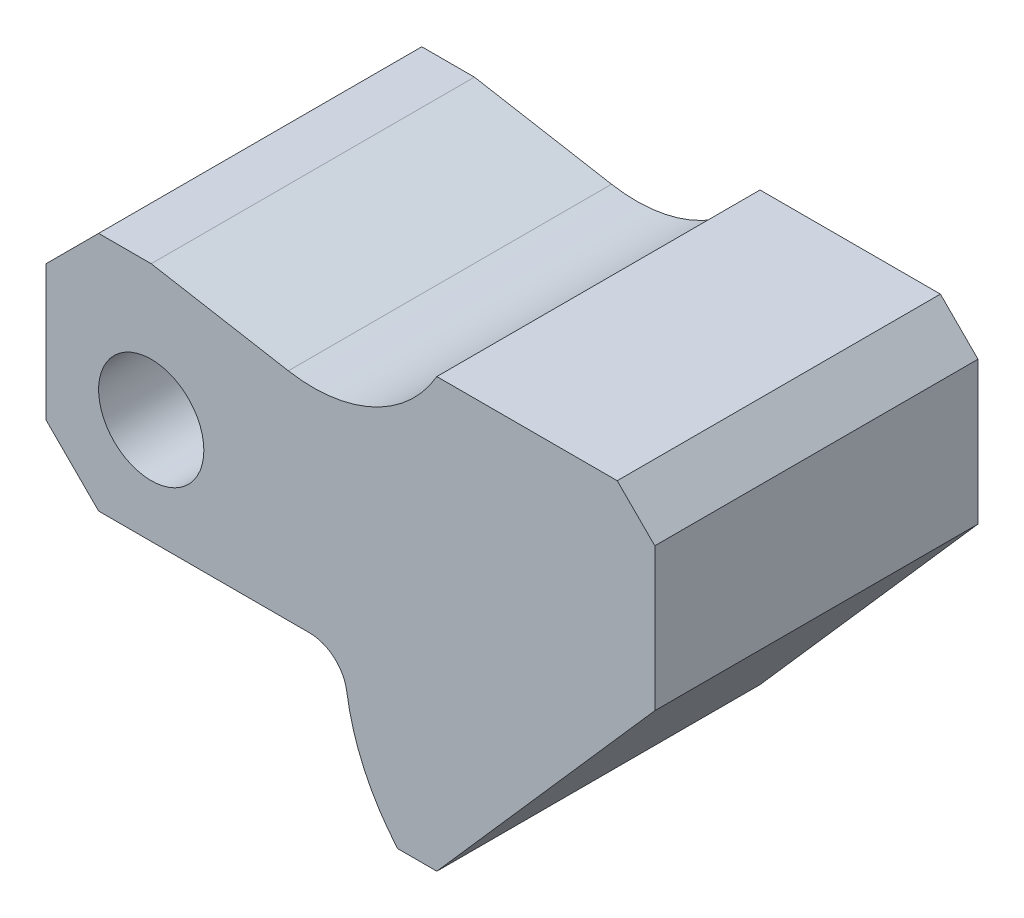
SolidWorks part; units mm, degrees
material "AISI 1020"
ref_plane "Front Plane" through (0, 0, 0) normal (0, 0, 1) x (1, 0, 0)
ref_plane "Top Plane" through (0, 0, 0) normal (0, 1, 0) x (1, 0, 0)
ref_plane "Right Plane" through (0, 0, 0) normal (1, 0, 0) x (0, 0, -1)
sketch "Sketch1" plane through (0, 0, 0) normal (0, 0, 1) x (1, 0, 0)
  line L0 (7, 19) -> (35.0666, 19)
  line L1 (0, 0) -> (81, 0)
  line L2 (0, 0) -> (0, 57)
  line L3 (0, 57) -> (81, 57)
  line L4 (81, 0) -> (81, 57)
  line L5 (0, 0) -> (81, 57) construction
  line L6 (0, 57) -> (81, 0) construction
  line L8 (81, 52) -> (76, 57)
  line L12 (0, 26) -> (7, 19)
  line L13 (0, 19) -> (7, 19)
  line L16 (81, 33) -> (52, 0)
  line L22 (0, 51) -> (14, 51)
  line L23 (0, 44) -> (7, 51)
  line L24 (14, 51) -> (52, 51) construction
  line L25 (35.5424, 66.4946) -> (35.5424, 47.4946) construction
  line L26 (14, 51) -> (32.2431, 47.7832)
  circle A0 centre (14, 33) radius 7
  arc A1 (32.2431, 47.7832) -> (52, 57) centre (35.5424, 66.4946) ccw
  arc A2 (46.7881, 0) -> (40.0123, 14.7353) centre (68.697, 19) cw
  arc A3 (40.0123, 14.7353) -> (35.0666, 19) centre (35.0666, 14) ccw
  point P4 (40.5, 28.5)
  point P16 (68.697, 19)
  dimension "D11" = 19
  dimension "D6" = 14
  dimension "D16" = 5
  dimension "D18" = 29
  dimension "D1" = 81
  dimension "D2" = 57
  dimension "D3" = 24
  dimension "D4" = 5
  dimension "D5" = 29
  dimension "D8" = 29
  dimension "D9" = 19
  dimension "D10" = 45
  dimension "D12" = 14
  dimension "D13" = 45
  dimension "D14" = 7
  dimension "D15" = 10
  dimension "D7" = 14
  dimension "D17" = 7
  dimension "D19" = 14
  dimension "D20" = 45
extrude "Boss-Extrude3" add sketch "Sketch1" along normal blind 43 contours A3 A2 L1 L16 L4 L8 L3 A1 L26 L22 L23 L2 L12 L0 A0 region at (44.6224, 33.3076, 0)
equation "\"A\"=81"
equation "\"D1@Sketch1\"=\"A\""
equation "\"B\"=57"
equation "\"D2@Sketch1\"=\"B\""
equation "\"C\"=43"
equation "\"D1@Boss-Extrude3\"=\"C\""
